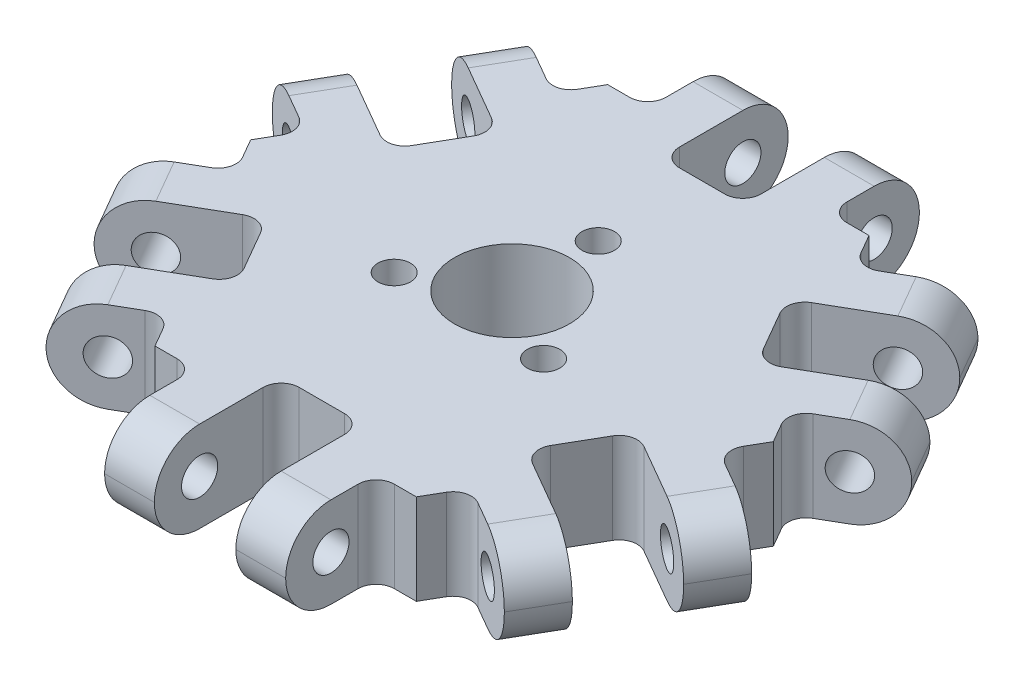
SolidWorks part; units mm, degrees
ref_plane "Front Plane" through (0, 0, 0) normal (0, 0, 1) x (1, 0, 0)
ref_plane "Top Plane" through (0, 0, 0) normal (0, 1, 0) x (1, 0, 0)
ref_plane "Right Plane" through (0, 0, 0) normal (1, 0, 0) x (0, 0, -1)
sketch "Sketch1" plane through (0, 0, 0) normal (0, 1, 0) x (1, 0, 0)
  line L0 (-28.8675, 0) -> (-14.4338, 25)
  line L1 (-14.4338, 25) -> (14.4338, 25)
  line L2 (14.4338, 25) -> (28.8675, 0)
  line L3 (28.8675, 0) -> (14.4338, -25)
  line L4 (14.4338, -25) -> (-14.4338, -25)
  line L5 (-14.4338, -25) -> (-28.8675, 0)
  line L6 (-14.4338, 25) -> (14.4338, -25) construction
  point P2 (0, 0)
  dimension "D1" = 50
  dimension "D2" = 120
  dimension "D3" = 120
extrude "Boss-Extrude1" add sketch "Sketch1" along normal blind 10
sketch "Sketch2" plane through (21.6506, 0, 12.5) normal (0.866, 0, 0.5) x (0.5, 0, -0.866)
  line L0 (-14.4338, 10) -> (14.4338, 10) construction
  line L1 (-10, 10) -> (10, 10)
  line L2 (-10, 10) -> (-10, 0)
  line L3 (-10, 0) -> (10, 0)
  line L4 (10, 10) -> (10, 0)
  line L5 (-14.4338, 0) -> (14.4338, 0) construction
  point P8 (0, 0)
  dimension "D1" = 20
extrude "Boss-Extrude2" add sketch "Sketch2" along normal blind 10 contours L2 L3 L4 L1
sketch "Sketch3" plane through (0, 10, 0) normal (0, 1, 0) x (1, 0, 0)
  line L0 (25.3109, -26.1603) -> (35.3109, -8.8397) construction
  line L1 (28.0609, -21.3971) -> (32.5609, -13.6029)
  line L2 (28.0609, -21.3971) -> (15.9365, -14.3971)
  line L3 (32.5609, -13.6029) -> (20.4365, -6.6029)
  line L4 (15.9365, -14.3971) -> (20.4365, -6.6029)
  line L7 (0, 0) -> (30.3109, -17.5) construction
  point P2 (30.3109, -17.5)
  dimension "D1" = 35
  dimension "D2" = 9
  dimension "D4" = 14
extrude "Cut-Extrude1" cut sketch "Sketch3" against normal up to next
fillet "Fillet1" radius 5 4 edges at (26.6859, 0, 23.7787) (26.6859, 10, 23.7787) (33.9359, 0, 11.2213) (33.9359, 10, 11.2213)
hole_wizard "Ø4.0 mm Dowel Holes1" positions "Sketch4" profile "Sketch5" hole size "Ø4.0" standard "ISO" end condition through all
sketch "Sketch4" plane through (-5, 0, 8.6603) normal (-0.5, 0, 0.866) x (0.866, 0, 0.5)
  point P0 (30, 5)
sketch "Sketch5" plane through (20.9808, 5, 23.6603) normal (0, 1, 0) x (0.866, 0, 0.5)
  line L0 (0, 0) -> (0, 49.3061)
  line L1 (0, 49.3061) -> (2, 49.3061)
  line L2 (2, 49.3061) -> (2, 0)
  line L5 (2, 0) -> (0, 0)
  line L11 (0, -6.35) -> (0, 107.95) construction
  dimension "Thru Hole Dia." = 4
  dimension "Thru Hole Depth" = 49.3061
ref_axis "Axis1" through (0, -0.5, 0) along (0, 1, 0)
pattern_circular "CirPattern5" count 6 over 360 about axis through (0, -0.5, 0) along (0, 1, 0) of "Boss-Extrude2", "Cut-Extrude1", "Fillet1", "Ø4.0 mm Dowel Holes1"
fillet "Fillet2" radius 2 24 edges at (26.6506, 5, -3.8397) (16.6506, 5, -21.1603) (15.9365, 5, -14.3971) (20.4365, 5, -6.6029) (-4.5, 5, -21) (10, 5, -25) (-15.9365, 5, -14.3971) (4.5, 5, -21) (-10, 5, -25) (-16.6506, 5, -21.1603) (-20.4365, 5, -6.6029) (-26.6506, 5, -3.8397) (-26.6506, 5, 3.8397) (-15.9365, 5, 14.3971) (-20.4365, 5, 6.6029) (-16.6506, 5, 21.1603) (-10, 5, 25) (4.5, 5, 21) (-4.5, 5, 21) (10, 5, 25) (16.6506, 5, 21.1603) (15.9365, 5, 14.3971) (20.4365, 5, 6.6029) (26.6506, 5, 3.8397)
sketch "Sketch6" plane through (0, 10, 0) normal (0, 1, 0) x (1, 0, 0)
  circle A0 centre (0, 0) radius 6.35
  dimension "D1" = 12.7
extrude "Cut-Extrude2" cut sketch "Sketch6" against normal through all
sketch "Sketch7" plane through (0, 10, 0) normal (0, 1, 0) x (1, 0, 0)
  circle A0 centre (0, 0) radius 9.525 construction
  dimension "D1" = 19.05
hole_wizard "M3 Clearance Hole1" positions "Sketch8" profile "Sketch9" hole size "M3" standard "ISO" end condition up to next
sketch "Sketch8" plane through (0, 10, 0) normal (0, 1, 0) x (1, 0, 0)
  circle A0 centre (0, 0) radius 9.525 construction
  point P0 (0, 9.525)
sketch "Sketch9" plane through (0, 10, -9.525) normal (1, 0, 0) x (0, 0, 1)
  line L0 (0, 0) -> (0, 10)
  line L1 (0, 10) -> (1.8, 10)
  line L2 (1.8, 10) -> (1.8, 0)
  line L5 (1.8, 0) -> (0, 0)
  line L11 (0, -6.35) -> (0, 107.95) construction
  dimension "Thru Hole Dia." = 3.6
  dimension "Thru Hole Depth" = 10
pattern_circular "CirPattern6" count 3 over 360 about axis through (0, -0.5, 0) along (0, 1, 0) of "M3 Clearance Hole1"
